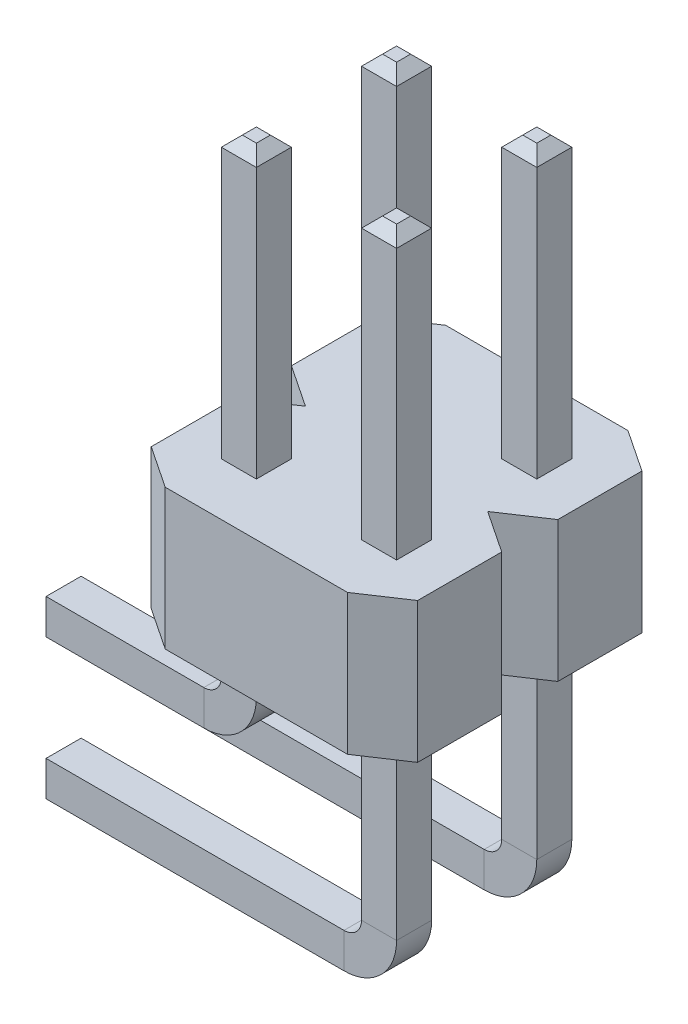
SolidWorks part; units mm, degrees
ref_plane "Front Plane" through (0, 0, 0) normal (0, 0, 1) x (1, 0, 0)
ref_plane "Top Plane" through (0, 0, 0) normal (0, 1, 0) x (1, 0, 0)
ref_plane "Right Plane" through (0, 0, 0) normal (1, 0, 0) x (0, 0, -1)
sketch "Sketch1" plane through (0, 0, 0) normal (0, 1, 0) x (1, 0, 0)
  line L0 (-2.413, -0.762) -> (-1.651, -1.27)
  line L1 (-1.651, -1.27) -> (1.651, -1.27)
  line L2 (-2.413, -0.762) -> (-2.413, 0.762)
  line L3 (-1.651, 1.27) -> (1.651, 1.27)
  line L4 (2.413, -0.762) -> (2.413, 0.762)
  line L5 (-2.413, -1.27) -> (2.413, 1.27) construction
  line L6 (-2.413, 1.27) -> (2.413, -1.27) construction
  line L7 (1.651, -1.27) -> (2.413, -0.762)
  line L8 (-2.413, 0.762) -> (-1.651, 1.27)
  line L9 (1.651, 1.27) -> (2.413, 0.762)
  point P0 (0, 0)
  dimension "D1" = 2.54
  dimension "D2" = 4.826
  dimension "D3" = 0.762
  dimension "D4" = 0.508
  dimension "D5" = 0.762
  dimension "D6" = 0.508
  dimension "D7" = 0.508
  dimension "D8" = 0.762
  dimension "D9" = 0.762
  dimension "D10" = 0.508
extrude "Boss-Extrude2" add sketch "Sketch1" along normal blind 2.54
sketch "Sketch2" plane through (0, 0, 0) normal (0, 0, 1) x (1, 0, 0)
  line L0 (-1.27, 2.54) -> (-1.27, 7.62)
  line L1 (0, -1.397) -> (0, 1.397) construction
  line L2 (1.27, 2.54) -> (1.27, 7.62)
  line L3 (-1.27, 2.54) -> (-1.27, -0.889)
  line L4 (-1.905, -1.524) -> (-4.953, -1.524)
  line L5 (1.27, 2.54) -> (1.27, -3.429)
  line L6 (0.635, -4.064) -> (-4.953, -4.064)
  line L7 (-1.651, 2.54) -> (1.651, 2.54) construction
  arc A0 (1.27, -3.429) -> (0.635, -4.064) centre (0.635, -3.429) cw
  arc A1 (-1.27, -0.889) -> (-1.905, -1.524) centre (-1.905, -0.889) cw
  dimension "D6" = 0.635
  dimension "D1" = 2.54
  dimension "D2" = 5.08
  dimension "D3" = 2.54
  dimension "D4" = 2.54
  dimension "D5" = 1.524
ref_plane "Plane1" through (0, 7.62, 0) normal (0, 1, 0) x (1, 0, 0)
sketch "Sketch3" plane through (0, 7.62, 0) normal (0, 1, 0) x (1, 0, 0)
  line L0 (0, -1.397) -> (0, 1.397) construction
  line L1 (-1.5875, -0.3175) -> (-0.9525, -0.3175)
  line L2 (-1.5875, -0.3175) -> (-1.5875, 0.3175)
  line L3 (-1.5875, 0.3175) -> (-0.9525, 0.3175)
  line L4 (-0.9525, -0.3175) -> (-0.9525, 0.3175)
  line L5 (-1.5875, -0.3175) -> (-0.9525, 0.3175) construction
  line L6 (-1.5875, 0.3175) -> (-0.9525, -0.3175) construction
  line L7 (1.5875, 0.3175) -> (0.9525, -0.3175) construction
  line L8 (1.5875, -0.3175) -> (0.9525, 0.3175) construction
  line L9 (0.9525, -0.3175) -> (0.9525, 0.3175)
  line L10 (1.5875, 0.3175) -> (0.9525, 0.3175)
  line L11 (1.5875, -0.3175) -> (1.5875, 0.3175)
  line L12 (1.5875, -0.3175) -> (0.9525, -0.3175)
  point P0 (-1.27, 0)
  point P12 (1.27, 0)
  dimension "D1" = 0.635
sketch "Sketch5" plane through (0, 7.62, 0) normal (0, 1, 0) x (1, 0, 0)
  line L0 (-1.5875, 0.3175) -> (-0.9525, 0.3175) construction
  line L1 (-0.9525, -0.3175) -> (-0.9525, 0.3175) construction
  line L2 (-1.5875, -0.3175) -> (-0.9525, -0.3175) construction
  line L3 (-1.5875, -0.3175) -> (-1.5875, 0.3175) construction
  line L4 (-1.5875, 0.3175) -> (-0.9525, 0.3175)
  line L5 (-0.9525, -0.3175) -> (-0.9525, 0.3175)
  line L6 (-1.5875, -0.3175) -> (-0.9525, -0.3175)
  line L7 (-1.5875, -0.3175) -> (-1.5875, 0.3175)
sketch "Sketch6" plane through (0, 7.62, 0) normal (0, 1, 0) x (1, 0, 0)
  line L0 (1.5875, 0.3175) -> (0.9525, 0.3175) construction
  line L1 (1.5875, -0.3175) -> (1.5875, 0.3175) construction
  line L2 (1.5875, -0.3175) -> (0.9525, -0.3175) construction
  line L3 (0.9525, -0.3175) -> (0.9525, 0.3175) construction
  line L4 (1.5875, 0.3175) -> (0.9525, 0.3175)
  line L5 (1.5875, -0.3175) -> (1.5875, 0.3175)
  line L6 (1.5875, -0.3175) -> (0.9525, -0.3175)
  line L7 (0.9525, -0.3175) -> (0.9525, 0.3175)
sweep "Sweep5" add profiles "Sketch5" path "Sketch2"
sketch "Sketch7" plane through (0, 0, 0) normal (0, 0, 1) x (1, 0, 0)
  line L0 (0.635, -4.064) -> (-4.953, -4.064) construction
  line L1 (1.27, 2.54) -> (1.27, -3.429) construction
  line L2 (1.27, 2.54) -> (1.27, 7.62) construction
  line L3 (0.635, -4.064) -> (-4.953, -4.064)
  line L4 (1.27, 2.54) -> (1.27, -3.429)
  line L5 (1.27, 2.54) -> (1.27, 7.62)
  arc A0 (0.635, -4.064) -> (1.27, -3.429) centre (0.635, -3.429) ccw construction
  arc A1 (0.635, -4.064) -> (1.27, -3.429) centre (0.635, -3.429) ccw
sweep "Sweep6" add profiles "Sketch6" path "Sketch7"
chamfer "Chamfer1" distance 0.1905 angle 45 16 edges at (-4.953, -4.064, -0.3175) (-4.953, -3.7465, 0) (-4.953, -4.064, 0.3175) (-4.953, -4.3815, 0) (-4.953, -1.2065, 0) (-4.953, -1.524, 0.3175) (-4.953, -1.8415, 0) (-4.953, -1.524, -0.3175) (-0.9525, 7.62, 0) (-1.27, 7.62, 0.3175) (-1.5875, 7.62, 0) (-1.27, 7.62, -0.3175) (1.27, 7.62, 0.3175) (0.9525, 7.62, 0) (1.27, 7.62, -0.3175) (1.5875, 7.62, 0)
mirror "Mirror1" about plane through (-1.651, 2.54, -1.27) normal (0, 0, 1) of bodies 105
sketch "Sketch8" plane through (0, 7.62, 0) normal (0, 1, 0) x (1, 0, 0)
  line L2 (-1.397, 2.413) -> (-1.143, 2.667) construction
  line L3 (1.143, 2.667) -> (1.397, 2.413) construction
  line L4 (1.143, -0.127) -> (1.397, 0.127) construction
  line L5 (-1.397, 0.127) -> (-1.143, -0.127) construction
  point P0 (-1.27, 0)
  point P1 (-1.27, 2.54)
  point P2 (1.27, 0)
  point P3 (1.27, 2.54)
